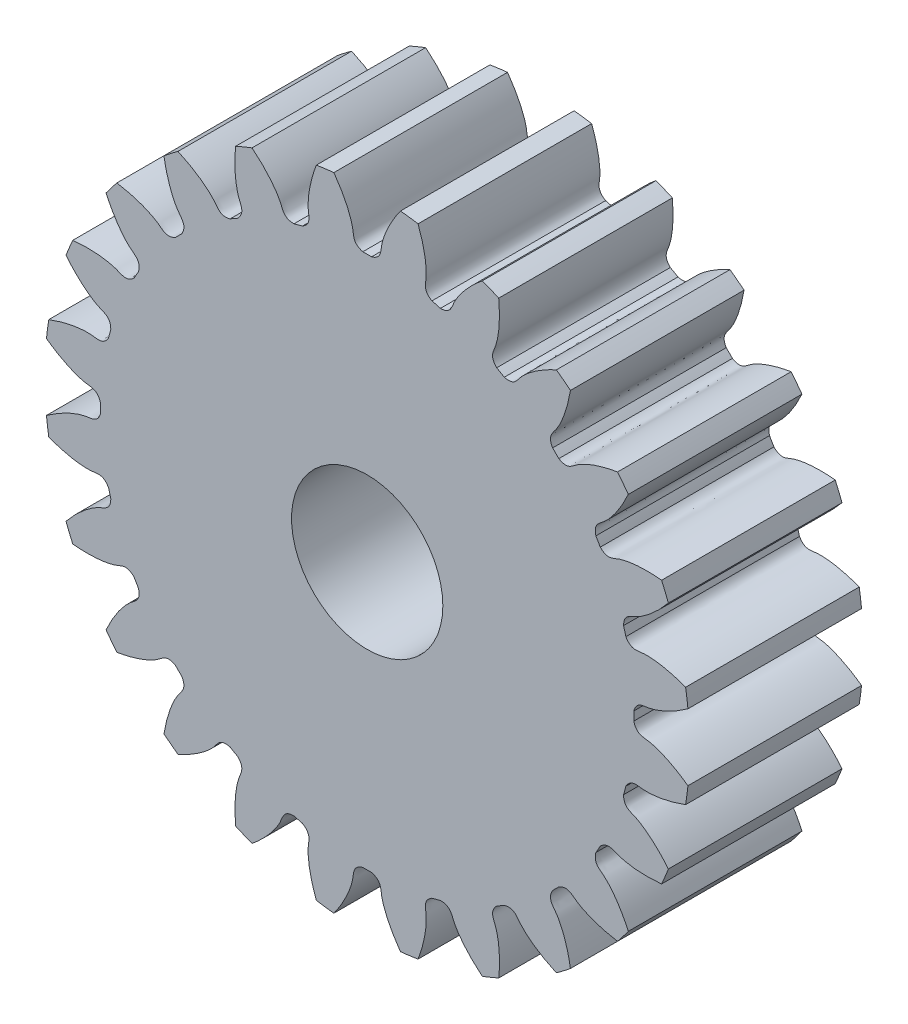
SolidWorks part; units mm, degrees
ref_plane "前视基准面" through (0, 0, 0) normal (0, 0, 1) x (1, 0, 0)
ref_plane "上视基准面" through (0, 0, 0) normal (0, 1, 0) x (1, 0, 0)
ref_plane "右视基准面" through (0, 0, 0) normal (1, 0, 0) x (0, 0, -1)
sketch "草图1" plane through (0, 0, 0) normal (0, 0, 1) x (1, 0, 0)
  circle A0 centre (0, 0) radius 6.5
extrude "凸台-拉伸1" add sketch "草图1" along normal blind 3.5
ref_axis "基准轴1" through (0, 0, 3.5) along (0, 0, -1)
sketch "草图2" plane through (0, 0, 0) normal (0, 0, 1) x (1, 0, 0)
  line L0 (0, 0) -> (0, 6.5) construction
  circle A0 centre (0, 0) radius 6.5 construction
  arc A1 (0.0884, 5.3743) -> (-0.0884, 5.3743) centre (0, 0) ccw
  arc A2 (1.5578, 7.3471) -> (-1.5578, 7.3471) centre (0, 0) ccw
  spline S0 degree 3 poles (0.0884, 5.3743) (0.284, 5.4284) (0.2695, 5.5579) (0.2931, 5.6863) (0.2965, 5.7029) (0.3007, 5.7216) (0.3058, 5.7424) (0.312, 5.7653) (0.3191, 5.7902) (0.3275, 5.8171) (0.3371, 5.846) (0.348, 5.8769) (0.3604, 5.9096) (0.3742, 5.9441) (0.3896, 5.9805) (0.4067, 6.0185) (0.4254, 6.0583) (0.446, 6.0997) (0.4684, 6.1427) (0.4928, 6.1872) (0.5192, 6.2332) (0.5476, 6.2806) (0.5782, 6.3293) (0.611, 6.3792) (0.6461, 6.4304) (0.6834, 6.4827) (0.7232, 6.536) (0.7654, 6.5903) (0.8101, 6.6456) (0.8574, 6.7016) (0.9073, 6.7583) (0.9598, 6.8158) (1.015, 6.8738) (1.0729, 6.9322) (1.1336, 6.9911) (1.1972, 7.0503) (1.2635, 7.1097) (1.3328, 7.1693) (1.4302, 7.2497) (1.506, 7.3084) (1.5578, 7.3471) knots 0 0 0 0 0.143961 0.149818 0.156577 0.164236 0.172796 0.182258 0.19262 0.203884 0.216049 0.229115 0.243082 0.25795 0.273719 0.290389 0.30796 0.326433 0.345806 0.366081 0.387257 0.409333 0.432311 0.45619 0.48097 0.506651 0.533234 0.560717 0.589101 0.618387 0.648574 0.679661 0.71165 0.74454 0.778331 0.813023 0.848616 0.885111 0.922506 1 1 1 1
  spline S1 degree 3 poles (-0.0884, 5.3743) (-0.284, 5.4284) (-0.2695, 5.5579) (-0.2931, 5.6863) (-0.2965, 5.7029) (-0.3007, 5.7216) (-0.3058, 5.7424) (-0.312, 5.7653) (-0.3191, 5.7902) (-0.3275, 5.8171) (-0.3371, 5.846) (-0.348, 5.8769) (-0.3604, 5.9096) (-0.3742, 5.9441) (-0.3896, 5.9805) (-0.4067, 6.0185) (-0.4254, 6.0583) (-0.446, 6.0997) (-0.4684, 6.1427) (-0.4928, 6.1872) (-0.5192, 6.2332) (-0.5476, 6.2806) (-0.5782, 6.3293) (-0.611, 6.3792) (-0.6461, 6.4304) (-0.6834, 6.4827) (-0.7232, 6.536) (-0.7654, 6.5903) (-0.8101, 6.6456) (-0.8574, 6.7016) (-0.9073, 6.7583) (-0.9598, 6.8158) (-1.015, 6.8738) (-1.0729, 6.9322) (-1.1336, 6.9911) (-1.1972, 7.0503) (-1.2635, 7.1097) (-1.3328, 7.1693) (-1.4302, 7.2497) (-1.506, 7.3084) (-1.5578, 7.3471) knots 0 0 0 0 0.143961 0.149818 0.156577 0.164236 0.172796 0.182258 0.19262 0.203884 0.216049 0.229115 0.243082 0.25795 0.273719 0.290389 0.30796 0.326433 0.345806 0.366081 0.387257 0.409333 0.432311 0.45619 0.48097 0.506651 0.533234 0.560717 0.589101 0.618387 0.648574 0.679661 0.71165 0.74454 0.778331 0.813023 0.848616 0.885111 0.922506 1 1 1 1
extrude "切除-拉伸1" cut sketch "草图2" along normal through all
pattern_circular "阵列(圆周)1" count 24 every 15 about axis through (0, 0, 3.5) along (0, 0, -1) of "切除-拉伸1"
sketch "草图3" plane through (0, 0, 0) normal (0, 0, 1) x (1, 0, 0)
  circle A0 centre (0, 0) radius 6 construction
  dimension "Dn" = 12
sketch "草图4" plane through (0, 0, 3.5) normal (0, 0, 1) x (1, 0, 0)
  circle A0 centre (0, 0) radius 1.525
  dimension "D1" = 3.05
extrude "切除-拉伸2" cut sketch "草图4" against normal up to next
